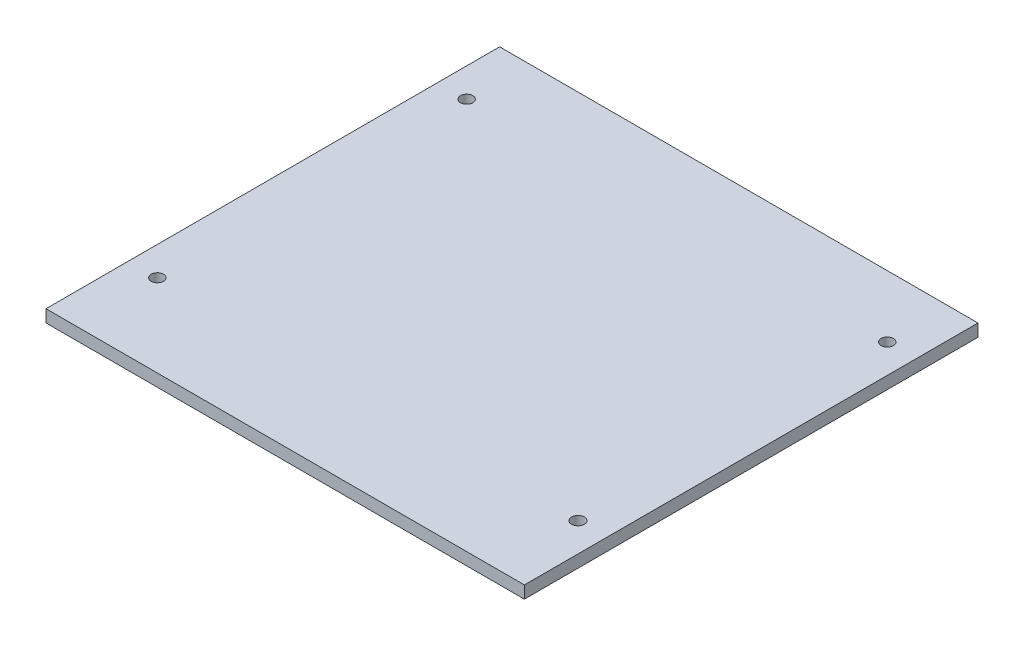
SolidWorks part; units mm, degrees
ref_plane "前视基准面" through (0, 0, 0) normal (0, 0, 1) x (1, 0, 0)
ref_plane "上视基准面" through (0, 0, 0) normal (0, 1, 0) x (1, 0, 0)
ref_plane "右视基准面" through (0, 0, 0) normal (1, 0, 0) x (0, 0, -1)
other "Configuration Table"
sketch "草图1" plane through (0, 0, 0) normal (0, 1, 0) x (1, 0, 0)
  line L1 (58, -55) -> (-58, -55)
  line L2 (58, -55) -> (58, 55)
  line L3 (58, 55) -> (-58, 55)
  line L4 (-58, -55) -> (-58, 55)
  line L5 (58, -55) -> (-58, 55) construction
  line L6 (58, 55) -> (-58, -55) construction
  point P0 (0, 0)
  dimension "D1" = 116
  dimension "D2" = 110
extrude "凸台-拉伸1" add sketch "草图1" along normal blind 3
sketch "草图2" plane through (0, 0, 0) normal (0, -1, 0) x (1, 0, 0)
  circle A0 centre (-51, 35) radius 1.5
  circle A1 centre (51, 35) radius 1.55
  circle A2 centre (51, -40) radius 1.5
  circle A3 centre (-51, -40) radius 1.5
extrude "切除-拉伸1" cut sketch "草图2" against normal blind 10
